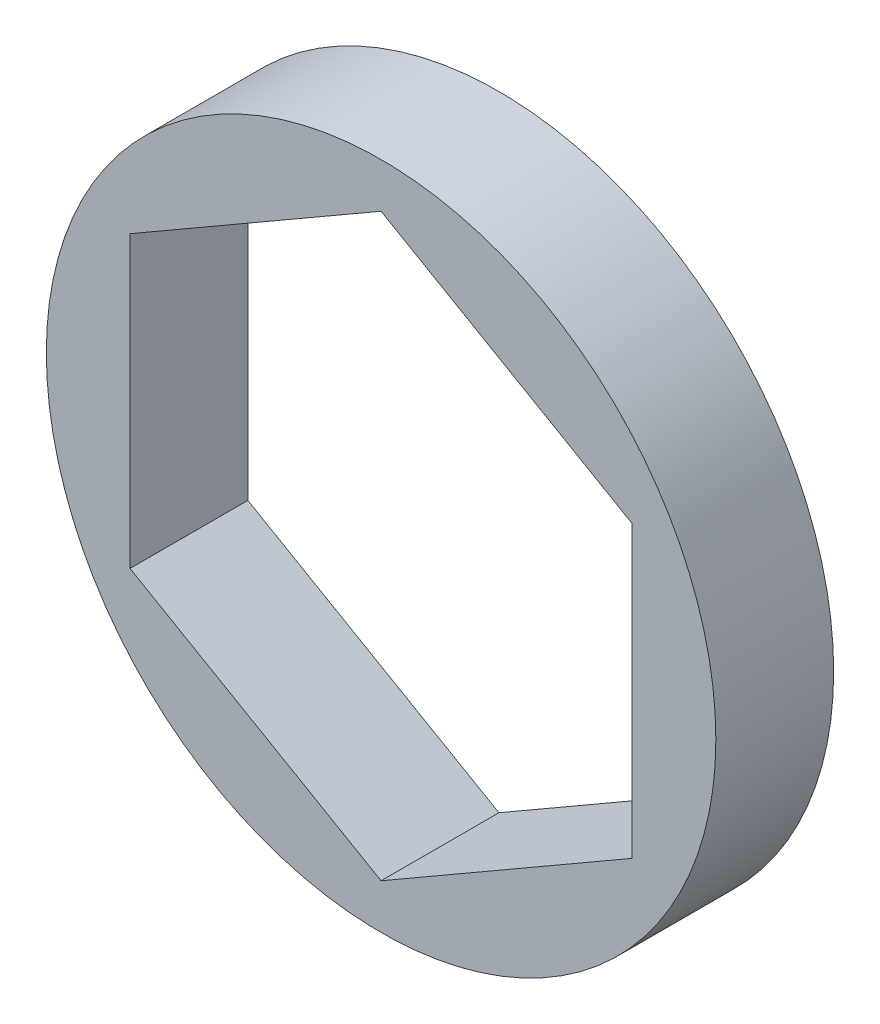
SolidWorks part; units mm, degrees
ref_plane "Front Plane" through (0, 0, 0) normal (0, 0, 1) x (1, 0, 0)
ref_plane "Top Plane" through (0, 0, 0) normal (0, 1, 0) x (1, 0, 0)
ref_plane "Right Plane" through (0, 0, 0) normal (1, 0, 0) x (0, 0, -1)
sketch "Sketch1" plane through (0, 0, 0) normal (0, 0, 1) x (1, 0, 0)
  line L1 (0, 5.4993) -> (-4.7625, 2.7496)
  line L2 (-4.7625, 2.7496) -> (-4.7625, -2.7496)
  line L3 (-4.7625, -2.7496) -> (0, -5.4993)
  line L4 (0, -5.4993) -> (4.7625, -2.7496)
  line L5 (4.7625, -2.7496) -> (4.7625, 2.7496)
  line L6 (4.7625, 2.7496) -> (0, 5.4993)
  circle A0 centre (0, 0) radius 4.7625 construction
  circle A1 centre (0, 0) radius 6.35
  dimension "D1" = 9.525
  dimension "D2" = 12.7
extrude "Boss-Extrude1" add sketch "Sketch1" along normal blind 2.2352
